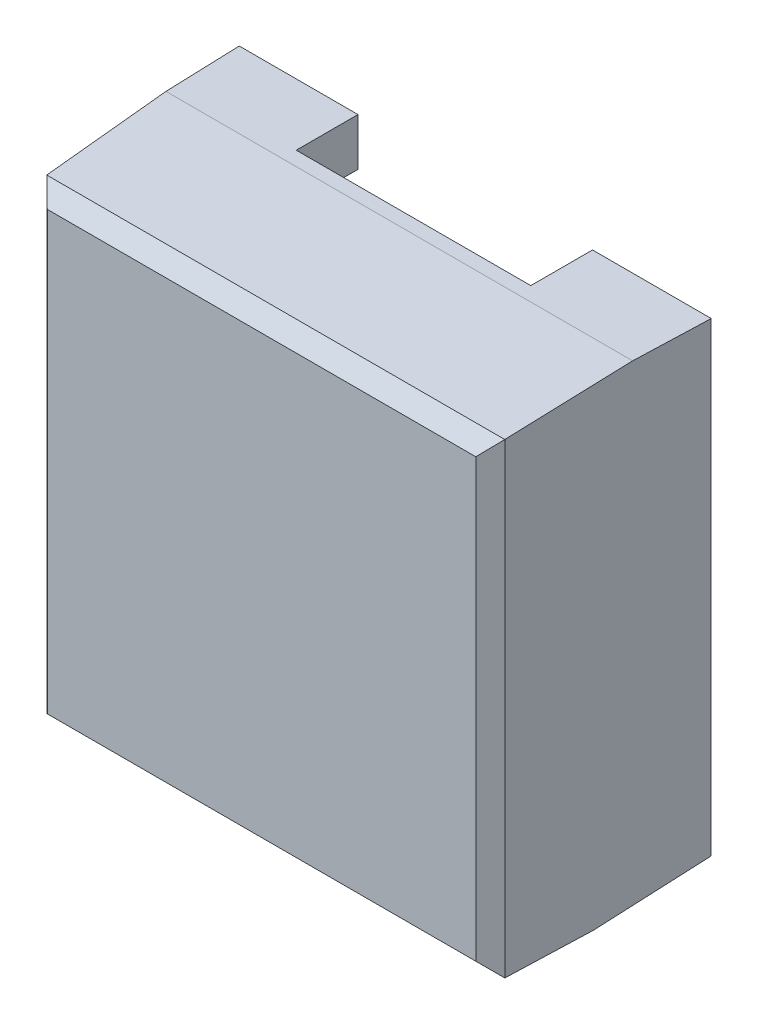
SolidWorks part; units mm, degrees
ref_plane "Front Plane" through (0, 0, 0) normal (0, 0, 1) x (1, 0, 0)
ref_plane "Top Plane" through (0, 0, 0) normal (0, 1, 0) x (1, 0, 0)
ref_plane "Right Plane" through (0, 0, 0) normal (1, 0, 0) x (0, 0, -1)
sketch "Sketch1" plane through (0, 0, 0) normal (0, 0, 1) x (1, 0, 0)
  line L1 (0, 0) -> (10, 0)
  line L2 (0, 0) -> (0, 10)
  line L3 (0, 10) -> (10, 10)
  line L4 (10, 0) -> (10, 10)
  dimension "D1" = 10
  dimension "D2" = 10
extrude "Boss-Extrude1" add sketch "Sketch1" along normal blind 4.5
chamfer "Chamfer1" distance 2.9 distance2 0.2 1 edges at (5, 10, 4.5)
chamfer "Chamfer3" distance 5.38 angle 2 2 edges at (0, 4.9, 4.5) (10, 4.9, 4.5)
chamfer "Chamfer4" distance 0.3 4 edges at (0.1879, 4.9, 4.5) (5, 0, 4.5) (9.8121, 4.9, 4.5) (5, 9.8, 4.5)
sketch "Sketch2" plane through (0, 0, 0) normal (0, 0, -1) x (-1, 0, 0)
  line L0 (-7.4693, 10) -> (-7.4693, 9)
  line L1 (-9.9693, 10) -> (-0.0307, 10) construction
  line L2 (-7.4693, 9) -> (-7.9693, 9)
  line L3 (-7.9693, 9) -> (-8.4693, 4)
  line L4 (-8.4693, 4) -> (-1.5307, 4)
  line L5 (-1.5307, 4) -> (-2.0307, 9)
  line L6 (-2.0307, 9) -> (-2.5307, 9)
  line L7 (-2.5307, 9) -> (-2.5307, 10)
  line L8 (-2.5307, 10) -> (-7.4693, 10)
  line L9 (-9.9693, 10) -> (-9.9693, 0) construction
  line L10 (-0.0307, 0) -> (-0.0307, 10) construction
  line L11 (-0.0307, 0) -> (-9.9693, 0) construction
  dimension "D1" = 1.5
  dimension "D2" = 1.5
  dimension "D3" = 2
  dimension "D4" = 2
  dimension "D5" = 2.5
  dimension "D6" = 2.5
  dimension "D7" = 4
  dimension "D8" = 1
  dimension "D9" = 1
extrude "Cut-Extrude1" cut sketch "Sketch2" against normal blind 1.3
chamfer "Chamfer5" distance 0.2 distance2 2.4 1 edges at (5, 0, 0)
